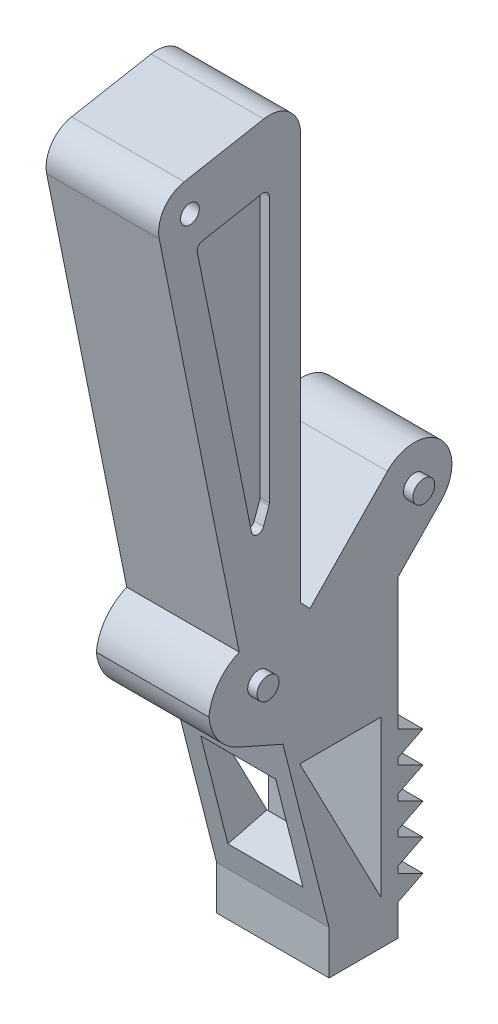
SolidWorks part; units mm, degrees
ref_plane "Front Plane" through (0, 0, 0) normal (0, 0, 1) x (1, 0, 0)
ref_plane "Top Plane" through (0, 0, 0) normal (0, 1, 0) x (1, 0, 0)
ref_plane "Right Plane" through (0, 0, 0) normal (1, 0, 0) x (0, 0, -1)
sketch "Sketch4" plane through (0, 0, 0) normal (1, 0, 0) x (0, 0, -1)
  line L0 (100.9932, 1.4556) -> (87.1936, 70.0819)
  line L1 (87.1936, 70.0819) -> (110.797, 74.427)
  line L2 (110.797, 74.427) -> (110.797, 3.427)
  line L3 (110.797, 3.427) -> (100.9932, 1.4556)
  line L4 (100.9932, 1.4556) -> (96.0914, 0.4699)
  line L5 (96.0914, 0.4699) -> (96.0914, -9.5301)
  line L6 (96.0914, -9.5301) -> (107.9808, -14.7876)
  line L7 (107.9808, -14.7876) -> (115.366, -43.8643)
  line L8 (115.366, -43.8643) -> (115.366, -50.8643)
  line L9 (115.366, -50.8643) -> (126.366, -50.8643)
  line L10 (126.366, -50.8643) -> (126.366, -0.8643)
  line L11 (110.797, 3.427) -> (112.2856, 1.8361)
  line L12 (133.3167, 6.3251) -> (124.6893, 14.6659) construction
  line L13 (126.366, -0.8643) -> (133.3167, 6.3251)
  line L14 (112.2856, 1.8361) -> (124.6893, 14.6659)
  arc A2 (133.3167, 6.3251) -> (124.6893, 14.6659) centre (129.003, 10.4955) ccw
  dimension "D1" = 70
  dimension "D2" = 71
  dimension "D3" = 10
  dimension "D4" = 24
  dimension "D5" = 15
  dimension "D6" = 10
  dimension "D7" = 13
  dimension "D8" = 30
  dimension "D9" = 7
  dimension "D10" = 11
  dimension "D11" = 50
  dimension "D12" = 12
  dimension "D13" = 10
extrude "Boss-Extrude1" add sketch "Sketch4" along normal mid plane 18 contours L3 L2 L1 L0 | L13 L12 L14 L11 L3 L4 L5 L6 L7 L8 L9 L10 | L12 A2 region at (0, 42.1454, -101.9664) region at (0, -15.5729, -116.7895) region at (0, 12.3263, -130.773)
sketch "Sketch5" plane through (9, 0, 0) normal (1, 0, 0) x (0, 0, -1)
  line L0 (123.666, -43.8643) -> (123.666, -18.8643)
  line L1 (123.666, -18.8643) -> (110.666, -18.8643)
  line L2 (110.666, -18.8643) -> (123.666, -43.8643)
  line L3 (115.366, -43.8643) -> (124.2784, -43.8643) construction
  line L4 (126.366, -50.8643) -> (126.366, -0.8643) construction
  dimension "D1" = 13
  dimension "D2" = 25
  dimension "D3" = 0
  dimension "D4" = 2.7
extrude "Cut-Extrude1" cut sketch "Sketch5" against normal blind 25
sketch "Sketch6" plane through (9, 0, 0) normal (1, 0, 0) x (0, 0, -1)
  line L0 (126.366, -45.8643) -> (130.366, -43.8643)
  line L1 (126.366, -50.8643) -> (126.366, -0.8643) construction
  line L2 (130.366, -43.8643) -> (126.366, -41.8643)
  line L3 (126.366, -41.8643) -> (126.366, -45.8643)
  line L4 (130.366, -43.8643) -> (126.366, -43.8643)
  line M13 (126.366, -50.8643) -> (126.366, -0.8643)
  dimension "D1" = 4
  dimension "D2" = 2
  dimension "D3" = 4
  dimension "D4" = 5
extrude "Boss-Extrude2" add sketch "Sketch6" against normal blind 18 contours L4 L2 L3 | L0 L4 M13 region at (9, -44.531, -127.6993) region at (9, -43.1977, -127.6993)
pattern_linear "LPattern1" count 5 spacing 5 along (0, 1, 0) of "Boss-Extrude2"
fillet "Fillet2" radius 8 2 edges at (0, -9.5301, -96.0914) (0, 0.4699, -96.0914)
fillet "Fillet3" radius 5 2 edges at (0, 74.427, -110.797) (0, 70.0819, -87.1936)
sketch "Sketch7" plane through (9, 0, 0) normal (1, 0, 0) x (0, 0, -1)
  circle A0 centre (93.0975, 66.0847) radius 1.5
  dimension "D1" = 3
extrude "Cut-Extrude2" cut sketch "Sketch7" against normal blind 25
sketch "Sketch8" plane through (0, 24.8677, -97.9088) normal (0, -0.2462, 0.9692) x (1, 0, 0)
  line L0 (0, -40.9144) -> (0, -70.9144) construction
  line L1 (9, -40.9144) -> (-9, -40.9144) construction
  line L2 (9, -70.9144) -> (-9, -70.9144) construction
  line L3 (-6, -48.4144) -> (6, -48.4144)
  line L4 (6, -48.4144) -> (6, -66.093)
  line L5 (6, -66.093) -> (-6, -66.093)
  line L6 (-6, -66.093) -> (-6, -48.4144)
  line L7 (9, -40.9144) -> (9, -70.9144) construction
  line L8 (-9, -40.9144) -> (-9, -70.9144) construction
  dimension "D1" = 7.5
  dimension "D2" = 3
  dimension "D3" = 3
  dimension "D4" = 12
  dimension "D5" = 6
sketch "Sketch9" plane through (0, 24.8677, -97.9088) normal (0, -0.2462, 0.9692) x (1, 0, 0)
extrude "Cut-Extrude4" cut sketch "Sketch8" against normal blind 8
sketch "Sketch10" plane through (9, 0, 0) normal (1, 0, 0) x (0, 0, -1)
  circle A0 centre (129.003, 10.4955) radius 1.75
  dimension "D1" = 3.5
extrude "Boss-Extrude3" add sketch "Sketch10" along normal blind 1.5
sketch "Sketch11" plane through (9, 0, 0) normal (1, 0, 0) x (0, 0, -1)
  circle A0 centre (104.0914, -4.3204) radius 1.75
  dimension "D1" = 3.5
extrude "Boss-Extrude5" add sketch "Sketch11" along normal blind 1.5
sketch "Sketch12" plane through (9, 0, 0) normal (1, 0, 0) x (0, 0, -1)
  line L0 (105.797, 62.1376) -> (105.797, 19.6789)
  line L1 (110.797, 68.4225) -> (110.797, 3.427) construction
  line L2 (94.2837, 60.1856) -> (102.9532, 17.0718)
  line L3 (100.9932, 1.4556) -> (88.1956, 65.099) construction
  line L4 (95.083, 61.3662) -> (104.6159, 63.1211)
  line L5 (92.1922, 71.0021) -> (104.8918, 73.3399) construction
  line L6 (104.8749, 16.9316) -> (105.7384, 19.3417)
  arc A0 (105.797, 62.1376) -> (104.6159, 63.1211) centre (104.797, 62.1376) ccw
  arc A1 (94.2837, 60.1856) -> (95.083, 61.3662) centre (95.264, 60.3827) cw
  arc A2 (105.797, 19.6789) -> (105.7384, 19.3417) centre (104.797, 19.6789) cw
  arc A3 (102.9532, 17.0718) -> (104.8749, 16.9316) centre (103.9335, 17.2689) ccw
  dimension "D1" = 1
  dimension "D2" = 1
  dimension "D3" = 5
  dimension "D4" = 5
  dimension "D5" = 10
extrude "Cut-Extrude5" cut sketch "Sketch12" against normal blind 1.5
ref_plane "Plane1" through (0, 0, 0) normal (1, 0, 0) x (0, 0, -1)
mirror "Mirror1" about plane through (0, 0, 0) normal (1, 0, 0) of "Boss-Extrude3", "Cut-Extrude5", "Boss-Extrude5"
